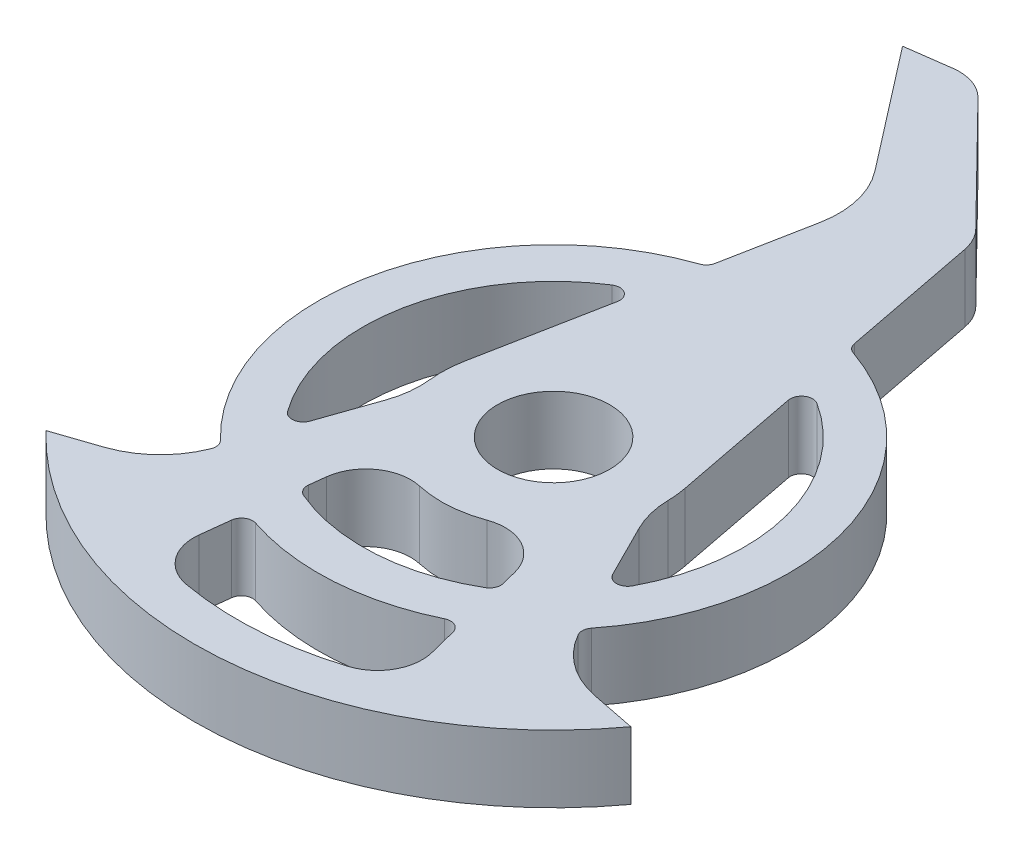
SolidWorks part; units mm, degrees
material "AISI Type A2 Tool Steel"
ref_plane "Front Plane" through (0, 0, 0) normal (0, 0, 1) x (1, 0, 0)
ref_plane "Top Plane" through (0, 0, 0) normal (0, 1, 0) x (1, 0, 0)
ref_plane "Right Plane" through (0, 0, 0) normal (1, 0, 0) x (0, 0, -1)
other "Center of Mass"
other "Bounding Box"
ref_plane "Default Plane" through (-8.9266, -12.7485, 0) normal (-0.1736, 0.9848, 0) x (0.9848, 0.1736, 0)
sketch "Sketch1" plane through (0, 0, 0) normal (0, 1, 0) x (1, 0, 0)
  line L0 (-15.5865, 3.0126) -> (-6.35, 50.8)
  line L1 (-6.35, 50.8) -> (-23.2013, 72.582)
  line L2 (15.5865, 3.0126) -> (6.35, 50.8)
  line L4 (-6.35, 50.8) -> (6.35, 50.8) construction
  line L5 (0, 50.8) -> (0, 0) construction
  line L6 (-23.2013, 72.582) -> (0, 0) construction
  line L7 (-23.2013, 72.582) -> (-13.7628, 73.8626)
  line L8 (-13.7628, 73.8626) -> (5.7363, 53.975)
  line L9 (5.7363, 53.975) -> (6.35, 50.8)
  circle A0 centre (0, 0) radius 7.9375
  arc A1 (-15.5865, 3.0126) -> (15.5865, 3.0126) centre (0, 0) ccw
  circle A2 centre (0, 0) radius 76.2 construction
  arc A4 (15.5865, 3.0126) -> (-15.5865, 3.0126) centre (0, 0) ccw construction
  dimension "D1" = 15.875
  dimension "D2" = 152.4
  dimension "D3" = 31.75
  dimension "D4" = 3.175
  dimension "D5" = 12.7
  dimension "D6" = 50.8
  dimension "D7" = 20
  dimension "D8" = 9.525
  dimension "D9" = 60
extrude "Boss-Extrude1" add sketch "Sketch1" along normal mid plane 9.525
fillet "Fillet6" radius 6.35 2 edges at (-13.7628, 0, -73.8626) (5.7363, 0, -53.975)
fillet "Fillet9" radius 12.7 1 edges at (-6.35, 0, -50.8)
sketch "Sketch4" plane through (0, 4.7625, 0) normal (0, 1, 0) x (1, 0, 0)
  circle A0 centre (0, 0) radius 33.3375
  circle A1 centre (0, 0) radius 26.9875
  dimension "D1" = 66.675
  dimension "D2" = 6.35
extrude "Boss-Extrude4" add sketch "Sketch4" against normal up to surface (9.525 mm away) up to face at (-6.3228, -4.7625, -45.9675)
sketch "Sketch2" plane through (0, 4.7625, 0) normal (0, 1, 0) x (1, 0, 0)
  line L0 (0, 0) -> (0, 50000) construction
  line L1 (-15.3133, -4.1855) -> (-24.6701, -31.0466)
  line L2 (-24.6701, -31.0466) -> (-36.6961, -35.1289)
  line L3 (15.7286, -2.1509) -> (28.5114, -27.5609)
  line L4 (28.5114, -27.5609) -> (40.9674, -30.0385)
  line L5 (3.3225, -50.6912) -> (0, 0) construction
  line L6 (-36.6961, -35.1289) -> (0, 0) construction
  line L7 (0, 0) -> (40.9674, -30.0385) construction
  line L8 (-36.6961, -35.1289) -> (2.1356, -32.5837) construction
  line L9 (2.1356, -32.5837) -> (40.9674, -30.0385) construction
  line L10 (-15.3133, -4.1855) -> (15.7286, -2.1509) construction
  line L11 (3.3225, -50.6912) -> (-3266.834, 49842.2549) construction
  arc A0 (-15.5865, 3.0126) -> (15.5865, 3.0126) centre (0, 0) ccw construction
  arc A1 (-36.6961, -35.1289) -> (40.9674, -30.0385) centre (0, 0) ccw
  circle A2 centre (0, 0) radius 76.2 construction
  arc A3 (-15.3133, -4.1855) -> (15.7286, -2.1509) centre (0, 0) ccw
  dimension "D1" = 25.4
  dimension "D2" = 25
  dimension "D3" = 25
  dimension "D4" = 100
  dimension "D5" = 3.175
  dimension "D6" = 12.7
  dimension "D7" = 3.75
extrude "Boss-Extrude2" add sketch "Sketch2" against normal up to surface (9.525 mm away) up to face at (-6.3228, -4.7625, -47.2253)
sketch "Sketch3" plane through (0, 4.7625, 0) normal (0, 1, 0) x (1, 0, 0)
  line L0 (-10.1613, -12.1969) -> (-11.5925, -24.3709)
  line L1 (11.6664, -10.7662) -> (14.6744, -22.6492)
  line L2 (-15.3133, -4.1855) -> (-10.1613, -12.1969) construction
  line L3 (11.6664, -10.7662) -> (15.7286, -2.1509) construction
  line L4 (-15.3133, -4.1855) -> (-20.1205, -17.9858) construction
  line L5 (-11.5925, -24.3709) -> (-12.367, -30.9588) construction
  line L6 (-12.367, -30.9588) -> (-13.7351, -42.5951)
  line L7 (14.6744, -22.6492) -> (16.3022, -29.0797) construction
  line L8 (16.3022, -29.0797) -> (19.1773, -40.4379)
  arc A0 (11.6664, -10.7662) -> (-10.1613, -12.1969) centre (0, 0) cw
  arc A1 (-15.5865, 3.0126) -> (15.5865, 3.0126) centre (0, 0) ccw construction
  arc A2 (-13.7351, -42.5951) -> (19.1773, -40.4379) centre (0, 0) ccw
  arc A4 (-11.5925, -24.3709) -> (14.6744, -22.6492) centre (0, 0) ccw
  arc A5 (-12.367, -30.9588) -> (16.3022, -29.0797) centre (0, 0) ccw
  arc A6 (25.4683, -21.5117) -> (10.0234, 31.795) centre (0, 0) ccw construction
  arc A7 (22.296, -15.2057) -> (11.4449, 24.4405) centre (0, 0) ccw construction
  arc A8 (-36.6961, -35.1289) -> (40.9674, -30.0385) centre (0, 0) ccw construction
  dimension "D1" = 6.0452
  dimension "D2" = 12.5
  dimension "D3" = 9.525
extrude "Cut-Extrude1" cut sketch "Sketch3" against normal through all
fillet "Fillet7" radius 6.35 4 edges at (11.6664, 0, 10.7662) (-10.1613, 0, 12.1969) (19.1773, 0, 40.4379) (-13.7351, 0, 42.5951)
fillet "Fillet8" radius 12.7 4 edges at (28.5114, 0, 27.5609) (15.7286, 0, 2.1509) (-15.3133, 0, 4.1855) (-24.6701, 0, 31.0466)
fillet "Fillet10" radius 1.5875 12 edges at (-11.5925, 0, 24.3709) (-12.367, 0, 30.9588) (16.3022, 0, 29.0797) (25.4683, 0, 21.5117) (14.6744, 0, 22.6492) (22.296, 0, 15.2057) (11.4449, 0, -24.4405) (10.0234, 0, -31.795) (-11.4449, 0, -24.4405) (-10.0234, 0, -31.795) (-20.1205, 0, 17.9858) (-22.4426, 0, 24.652)
